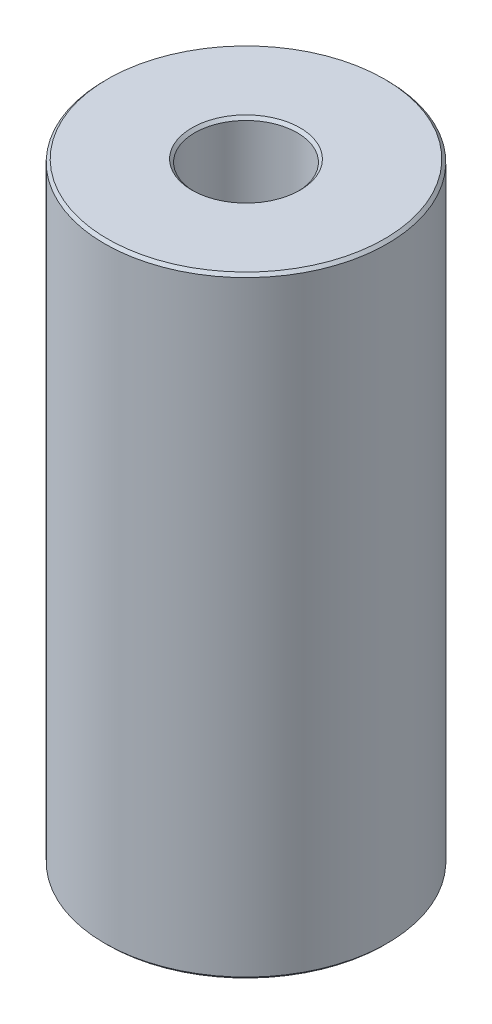
SolidWorks part; units mm, degrees
ref_plane "Front Plane" through (0, 0, 0) normal (0, 0, 1) x (1, 0, 0)
ref_plane "Top Plane" through (0, 0, 0) normal (0, 1, 0) x (1, 0, 0)
ref_plane "Right Plane" through (0, 0, 0) normal (1, 0, 0) x (0, 0, -1)
sketch "Sketch1" plane through (0, 0, 0) normal (0, 1, 0) x (1, 0, 0)
  circle A0 centre (0, 0) radius 17.5
  dimension "SLEEVE_OD" = 35
extrude "Boss-Extrude1" add sketch "Sketch1" along normal blind 75.7217
sketch "Sketch2" plane through (0, 0, 0) normal (0, 1, 0) x (1, 0, 0)
  circle A0 centre (0, 0) radius 6.3458
  dimension "BORE_D" = 12.6917
extrude "Cut-Extrude1" cut sketch "Sketch2" along normal through all
chamfer "Chamfer1" distance 0.3501 angle 45 4 edges at (0, 75.7217, 6.3458) (0, 0, 6.3458) (0, 0, 17.5) (0, 75.7217, 17.5)
